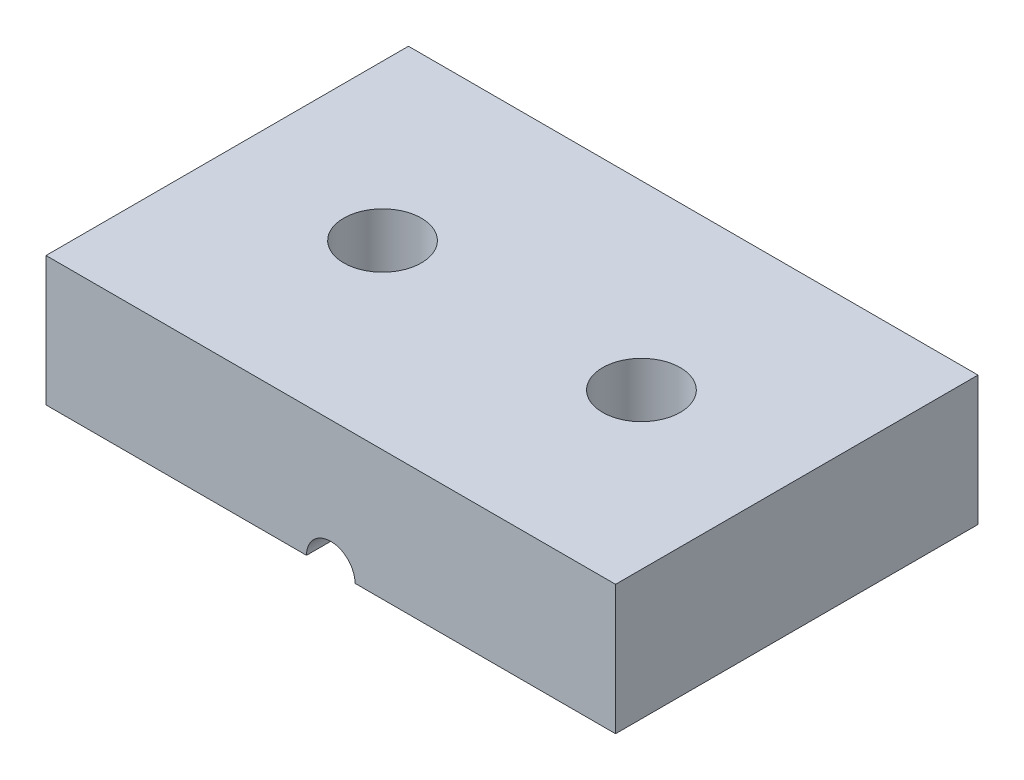
SolidWorks part; units mm, degrees
ref_plane "Front Plane" through (0, 0, 0) normal (0, 0, 1) x (1, 0, 0)
ref_plane "Top Plane" through (0, 0, 0) normal (0, 1, 0) x (1, 0, 0)
ref_plane "Right Plane" through (0, 0, 0) normal (1, 0, 0) x (0, 0, -1)
sketch "Sketch1" plane through (0, 0, 0) normal (0, 1, 0) x (1, 0, 0)
  line L1 (0, 0) -> (8.8, 0)
  line L2 (0, 0) -> (0, 5.6)
  line L3 (0, 5.6) -> (8.8, 5.6)
  line L4 (8.8, 0) -> (8.8, 5.6)
  dimension "D1" = 8.8
  dimension "D2" = 5.6
extrude "Boss-Body" add sketch "Sketch1" along normal blind 2
sketch "Sketch2" plane through (0, 2, 0) normal (0, 1, 0) x (1, 0, 0)
  line L0 (0, 2.8) -> (8.8, 2.8) construction
  line L1 (0, 5.6) -> (0, 0) construction
  line L2 (8.8, 0) -> (8.8, 5.6) construction
  line L3 (2.4, 2.8) -> (6.4, 2.8) construction
  circle A0 centre (2.4, 2.8) radius 0.6
  circle A1 centre (6.4, 2.8) radius 0.6
  point P9 (4.4, 2.8)
  dimension "D2" = 1.2
  dimension "D1" = 4
extrude "Cut-Screw Through Holes" cut sketch "Sketch2" against normal through all
sketch "Sketch3" plane through (0, 0, 0) normal (0, 0, 1) x (1, 0, 0)
  line L0 (0, 0) -> (8.8, 0) construction
  circle A0 centre (4.4, 0) radius 0.375
  dimension "D1" = 0.75
extrude "Cut-Cable Pass" cut sketch "Sketch3" against normal through all
